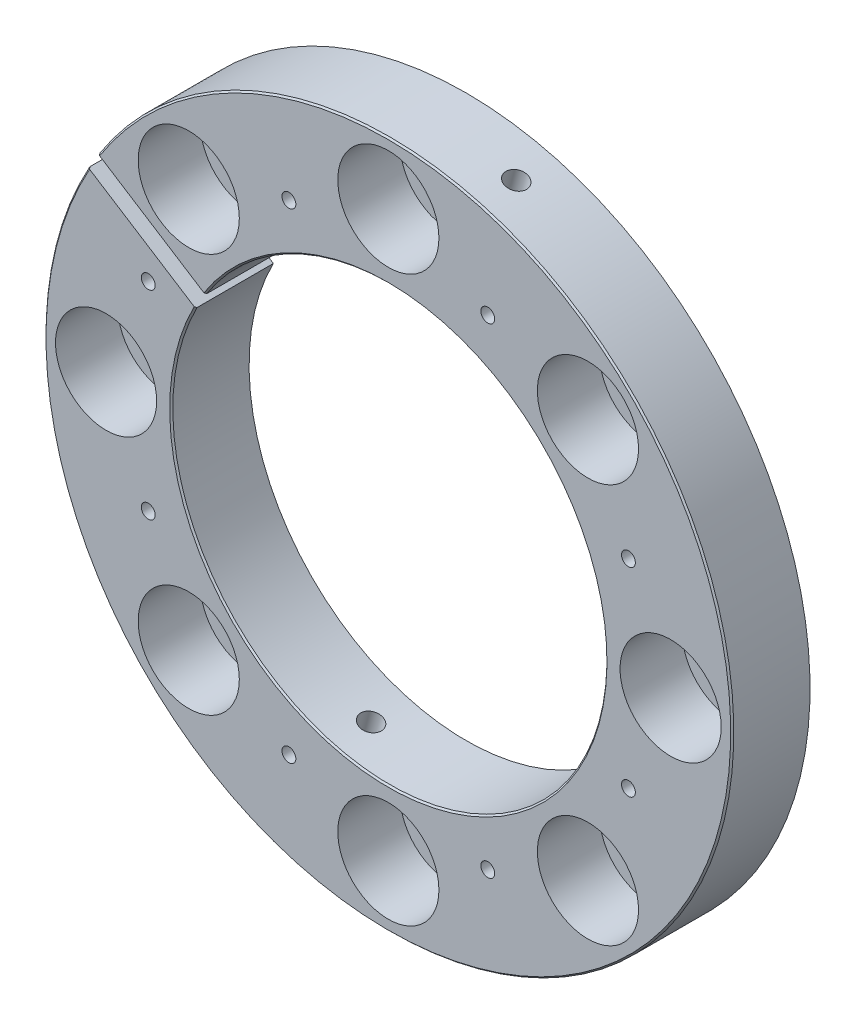
SolidWorks part; units mm, degrees
ref_plane "Front" through (0, 0, 0) normal (0, 0, 1) x (1, 0, 0)
ref_plane "Top" through (0, 0, 0) normal (0, 1, 0) x (1, 0, 0)
ref_plane "Right" through (0, 0, 0) normal (1, 0, 0) x (0, 0, -1)
sketch "Sketch2" plane through (0, 0, 0) normal (0, 0, 1) x (1, 0, 0)
  circle A0 centre (0, 0) radius 56.134
  dimension "D1" = 112.268
extrude "Boss-Extrude1" add sketch "Sketch2" along normal blind 12.7
sketch "Sketch3" plane through (0, 0, 12.7) normal (0, 0, 1) x (1, 0, 0)
  circle A0 centre (0, 0) radius 35.433
  dimension "D1" = 70.866
extrude "Cut-Extrude1" cut sketch "Sketch3" against normal through all
chamfer "Chamfer1" distance 0.254 angle 45 2 edges at (56.134, 0, 12.7) (35.433, 0, 12.7)
sketch "Sketch17" plane through (0, 0, 12.7) normal (0, 0, 1) x (1, 0, 0)
  circle A0 centre (0, 0) radius 46.0756
  dimension "D1" = 92.1512
hole_wizard "CBORE for 5/16 Hex Head Bolt2" positions "Sketch19" profile "Sketch18" counterbore size "5/16" standard "ANSI Inch" end condition through all
sketch "Sketch19" plane through (0, 0, 12.7) normal (0, 0, 1) x (1, 0, 0)
  circle A0 centre (0, 0) radius 46.0756 construction
  point P0 (0, 46.0756)
sketch "Sketch18" plane through (0, 46.0756, 12.7) normal (1, 0, 0) x (0, -1, 0)
  line L0 (0, 0) -> (0, 12.7)
  line L1 (0, 12.7) -> (4.2164, 12.7)
  line L3 (4.2164, 12.7) -> (4.2164, 10.16)
  line L4 (4.2164, 10.16) -> (8.255, 10.16)
  line L5 (8.255, 10.16) -> (8.255, 0)
  line L7 (8.255, 0) -> (0, 0)
  line L11 (0, -6.35) -> (0, 107.95) construction
  dimension "Thru Hole Dia." = 8.4328
  dimension "Thru Hole Depth" = 12.7
  dimension "C'Bore Dia." = 16.51
  dimension "C'Bore Depth" = 10.16
pattern_circular "CirPattern1" count 8 over 360 about axis through (0, 0, 0) along (0, 0, 1) of "CBORE for 5/16 Hex Head Bolt2" reverse direction yes
sketch "Sketch20" plane through (0, 0, 12.7) normal (0, 0, 1) x (1, 0, 0)
  line L0 (0, 0) -> (0, 60.8945) construction
  line L1 (0, 0) -> (-25.0446, 60.4631) construction
  line L2 (0, 0) -> (-78.5536, 32.538) construction
  line L3 (0, 0) -> (-69.5155, 44.2862) construction
  line L4 (0, 0) -> (-58.1527, 37.0474)
  line L5 (-58.1527, 37.0474) -> (-59.8586, 34.3696)
  line L6 (-59.8586, 34.3696) -> (-1.7059, -2.6778)
  line L7 (-1.7059, -2.6778) -> (0, 0)
  line L8 (0, 0) -> (18.0261, 67.2742) construction
  circle A0 centre (0, 0) radius 42.418
  dimension "D1" = 84.836
  dimension "D2" = 22.5
  dimension "D3" = 45
  dimension "D4" = 10
  dimension "D5" = 3.175
  dimension "D6" = 15
hole_wizard "#4-40 Tapped Hole1" positions "Sketch22" profile "Sketch21" tap size "#4-40" standard "ANSI Inch"
sketch "Sketch22" plane through (0, 0, 12.7) normal (0, 0, 1) x (1, 0, 0)
  line L0 (0, 0) -> (-25.0446, 60.4631) construction
  circle A0 centre (0, 0) radius 42.418 construction
  point P0 (-16.2327, 39.1891)
cosmetic thread "Hole Thread1" parameters "D1"=3.048, "D2"=2.8448
sketch "Sketch21" plane through (-16.2327, 39.1891, 12.7) normal (1, 0, 0) x (0, -1, 0)
  line L0 (0, 0) -> (0, 8.2738)
  line L1 (0, 8.2738) -> (1.1303, 7.5946)
  line L2 (1.1303, 7.5946) -> (1.1303, 0)
  line L5 (1.1303, 0) -> (0, 0)
  line L10 (0, 8.2738) -> (-1.1303, 7.5946) construction
  line L11 (0, -6.35) -> (0, 107.95) construction
  dimension "Tap Drill Dia." = 2.2606
  dimension "Tap Drill Depth" = 7.5946
  dimension "Drill Angle" = 118
ref_axis "Axis1" through (0, 0, 0) along (0, 0, 1)
pattern_circular "CirPattern2" count 8 over 360 about axis through (0, 0, 0) along (0, 0, 1) of "#4-40 Tapped Hole1"
sketch "Sketch26" plane through (0, 0, 12.7) normal (0, 0, 1) x (1, 0, 0)
  line L0 (0, 0) -> (-58.1527, 37.0474)
  line L1 (-58.1527, 37.0474) -> (-59.8586, 34.3696)
  line L2 (-59.8586, 34.3696) -> (-1.7059, -2.6778)
  line L3 (-1.7059, -2.6778) -> (0, 0)
extrude "Cut-Extrude2" cut sketch "Sketch26" against normal through all
sketch "Sketch27" plane through (0, 0, 0) normal (0, 0, -1) x (-1, 0, 0)
  line L0 (0, 0) -> (-18.0261, 67.2742) construction
hole_wizard "#8-32 Tapped Hole2" positions "3DSketch2" profile "Sketch28" tap size "#8-32" standard "ANSI Inch" end condition through all
sketch3d "3DSketch2"
  line L0 (0, 0, 0) -> (18.0261, 67.2742, 0) construction
  line L1 (0, 0, 12.7) -> (18.0261, 67.2742, 12.7) construction
  point P0 (14.5285, 54.2213, 6.35)
  dimension "D1" = 6.35
  dimension "D2" = 6.35
sketch "Sketch28" plane through (14.5285, 54.2213, 6.35) normal (0, 0, 1) x (-0.9659, 0.2588, 0)
  line L0 (0, 0) -> (0, 124.8838)
  line L1 (0, 124.8838) -> (1.7272, 124.8838)
  line L2 (1.7272, 124.8838) -> (1.7272, 0)
  line L5 (1.7272, 0) -> (0, 0)
  line L11 (0, -6.35) -> (0, 107.95) construction
  dimension "Thru Tap Drill Dia." = 3.4544
  dimension "Thru Tap Drill Depth" = 124.8838
cosmetic thread "Hole Thread3" parameters "D2"=4.1656
